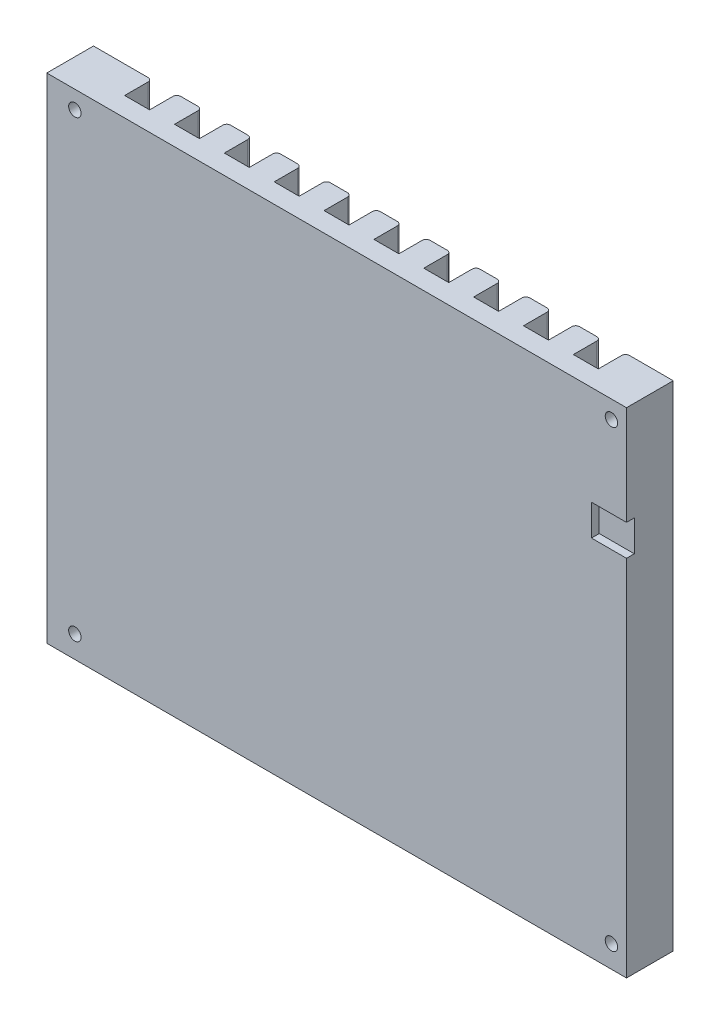
SolidWorks part; units mm, degrees
ref_plane "前视基准面" through (0, 0, 0) normal (0, 0, 1) x (1, 0, 0)
ref_plane "上视基准面" through (0, 0, 0) normal (0, 1, 0) x (1, 0, 0)
ref_plane "右视基准面" through (0, 0, 0) normal (1, 0, 0) x (0, 0, -1)
other "Configuration Table"
sketch "草图1" plane through (0, 0, 0) normal (0, 0, 1) x (1, 0, 0)
  line L0 (74.42, 63.4) -> (74.42, 50.65)
  line L1 (0, 0) -> (74.42, 0)
  line L2 (0, 0) -> (0, 63.4)
  line L3 (0, 63.4) -> (74.42, 63.4)
  line L4 (74.42, 0) -> (74.42, 63.4)
  line L5 (74.42, 50.65) -> (69.92, 50.65)
  line L6 (69.92, 50.65) -> (69.92, 46.66)
  line L7 (69.92, 46.66) -> (74.42, 46.66)
  line L8 (74.42, 46.66) -> (74.42, 0)
  dimension "D1" = 63.4
  dimension "D2" = 74.42
  dimension "D3" = 12.75
  dimension "D4" = 4.5
  dimension "D5" = 3.99
extrude "凸台-拉伸1" add sketch "草图1" against normal blind 6 contours L6 L7 L4 L5 | L7 L6 L5 L0 L3 L2 L1 L4 region at (37.0765, 31.6352, 0) region at (72.17, 48.655, 0)
extrude "切除-拉伸1" cut sketch "草图1<3>" against normal blind 1 contours L6 L7 L4 L5 region at (72.17, 48.655, 0)
sketch "草图1<3>" plane through (0, 0, 0) normal (0, 0, 1) x (1, 0, 0) same geometry as "草图1"
hole_wizard "M2 螺纹孔10" positions "草图17" profile "草图18" tap size "M2" standard "GB" end condition through all
sketch "草图17" plane through (0, 0, 0) normal (0, 0, 1) x (1, 0, 0)
  point P0 (3.61, 61.113)
  point P3 (72.488, 61.113)
  point P6 (72.488, 2.851)
  point P9 (3.61, 2.851)
sketch "草图18" plane through (3.61, 61.113, 0) normal (1, 0, 0) x (0, -1, 0)
  line L0 (0, 0) -> (0, 6)
  line L1 (0, 6) -> (0.8, 6)
  line L2 (0.8, 6) -> (0.8, 0)
  line L5 (0.8, 0) -> (0, 0)
  line L11 (0, -6.35) -> (0, 107.95) construction
  dimension "通孔螺纹孔钻头直径" = 1.6
  dimension "通孔螺纹孔钻头深度" = 6
cosmetic thread "孔螺纹线10" parameters "D2"=2
cosmetic thread "孔螺纹线11" parameters "D2"=2
cosmetic thread "孔螺纹线12" parameters "D2"=2
cosmetic thread "孔螺纹线13" parameters "D2"=2
sketch "草图19" plane through (0, 0, 0) normal (0, -1, 0) x (1, 0, 0)
  line L0 (10.7, -6) -> (13.9, -6)
  line L1 (17.1, -6) -> (20.3, -6)
  line L2 (0, -6) -> (74.42, -6) construction
  line L3 (17.1, -2.5) -> (17.1, -6)
  line L4 (0, -6) -> (7.5, -6)
  line L5 (7.5, -6) -> (7.5, -2.5)
  line L6 (7.5, -2.5) -> (10.7, -2.5)
  line L7 (10.7, -2.5) -> (10.7, -6)
  line L8 (13.9, -2.5) -> (17.1, -2.5)
  line L9 (13.9, -6) -> (13.9, -2.5)
  line L10 (23.5, -6) -> (26.7, -6)
  line L11 (23.5, -2.5) -> (23.5, -6)
  line L12 (20.3, -2.5) -> (23.5, -2.5)
  line L13 (20.3, -6) -> (20.3, -2.5)
  line L14 (29.9, -6) -> (33.1, -6)
  line L15 (29.9, -2.5) -> (29.9, -6)
  line L16 (26.7, -2.5) -> (29.9, -2.5)
  line L17 (26.7, -6) -> (26.7, -2.5)
  line L18 (36.3, -6) -> (39.5, -6)
  line L19 (36.3, -2.5) -> (36.3, -6)
  line L20 (33.1, -2.5) -> (36.3, -2.5)
  line L21 (33.1, -6) -> (33.1, -2.5)
  line L22 (42.7, -6) -> (45.9, -6)
  line L23 (42.7, -2.5) -> (42.7, -6)
  line L24 (39.5, -2.5) -> (42.7, -2.5)
  line L25 (39.5, -6) -> (39.5, -2.5)
  line L26 (49.1, -6) -> (52.3, -6)
  line L27 (49.1, -2.5) -> (49.1, -6)
  line L28 (45.9, -2.5) -> (49.1, -2.5)
  line L29 (45.9, -6) -> (45.9, -2.5)
  line L30 (55.5, -6) -> (58.7, -6)
  line L31 (55.5, -2.5) -> (55.5, -6)
  line L32 (52.3, -2.5) -> (55.5, -2.5)
  line L33 (52.3, -6) -> (52.3, -2.5)
  line L34 (61.9, -6) -> (65.1, -6)
  line L35 (61.9, -2.5) -> (61.9, -6)
  line L36 (58.7, -2.5) -> (61.9, -2.5)
  line L37 (58.7, -6) -> (58.7, -2.5)
  line L38 (68.3, -6) -> (71.5, -6)
  line L39 (68.3, -2.5) -> (68.3, -6)
  line L40 (65.1, -2.5) -> (68.3, -2.5)
  line L41 (65.1, -6) -> (65.1, -2.5)
  line L42 (71.5, -6) -> (74.42, -6)
  line M8 (0, -6) -> (74.42, -6)
  dimension "D1" = 7.5
  dimension "D2" = 3.5
  dimension "D3" = 3.2
  dimension "D4" = 10
extrude "切除-拉伸2" cut sketch "草图19" against normal through all and the other way through all contours L7 L6 L5 M8 | L9 L3 L8 M8 | L13 L11 L12 M8 | L17 L15 L16 M8 | L21 L19 L20 M8 | L25 L23 L24 M8 | L29 L27 L28 M8 | L33 L31 L32 M8 | L37 L35 L36 M8 | L41 L39 L40 M8 region at (66.7, 0, -4.25) region at (60.3, 0, -4.25) region at (53.9, 0, -4.25) region at (47.5, 0, -4.25) region at (41.1, 0, -4.25) region at (34.7, 0, -4.25) region at (28.3, 0, -4.25) region at (21.9, 0, -4.25) region at (15.5, 0, -4.25) region at (9.1, 0, -4.25)
fillet "圆角2" radius 0.5 20 edges at (68.3, 31.7, -6) (61.9, 31.7, -6) (55.5, 31.7, -6) (49.1, 31.7, -6) (42.7, 31.7, -6) (36.3, 31.7, -6) (29.9, 31.7, -6) (23.5, 31.7, -6) (17.1, 31.7, -6) (10.7, 31.7, -6) (65.1, 31.7, -6) (58.7, 31.7, -6) (52.3, 31.7, -6) (45.9, 31.7, -6) (39.5, 31.7, -6) (33.1, 31.7, -6) (26.7, 31.7, -6) (20.3, 31.7, -6) (13.9, 31.7, -6) (7.5, 31.7, -6)
